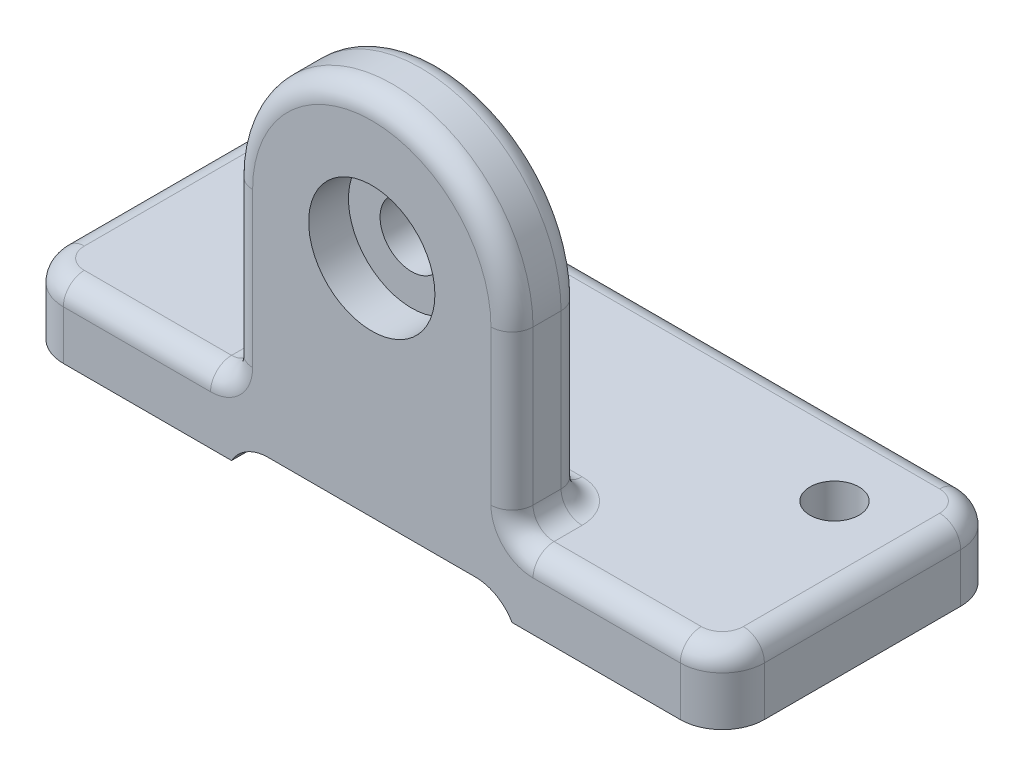
SolidWorks part; units mm, degrees
ref_plane "Front Plane" through (0, 0, 0) normal (0, 0, 1) x (1, 0, 0)
ref_plane "Top Plane" through (0, 0, 0) normal (0, 1, 0) x (1, 0, 0)
ref_plane "Right Plane" through (0, 0, 0) normal (1, 0, 0) x (0, 0, -1)
sketch "Sketch1" plane through (0, 0, 0) normal (0, 1, 0) x (1, 0, 0)
  line L1 (0, 0) -> (100, 0)
  line L2 (0, 0) -> (0, 40)
  line L3 (0, 40) -> (100, 40)
  line L4 (100, 0) -> (100, 40)
  dimension "D1" = 100
  dimension "D2" = 40
extrude "Base Plate" add sketch "Sketch1" along normal blind 10
sketch "Sketch2" plane through (0, 0, 0) normal (0, 0, 1) x (1, 0, 0)
  line L0 (30, 0) -> (30, 35)
  line L1 (0, 0) -> (100, 0) construction
  line L2 (70, 35) -> (70, 0)
  line L3 (70, 0) -> (30, 0)
  line L4 (0, 10) -> (0, 0) construction
  arc A0 (30, 35) -> (70, 35) centre (50, 35) cw
  dimension "D1" = 20
  dimension "D2" = 50
  dimension "D3" = 35
extrude "Vert Boss" add sketch "Sketch2" against normal blind 10
sketch "Sketch5" plane through (0, 0, 0) normal (0, 0, 1) x (1, 0, 0)
  line L0 (0, 0) -> (100, 0) construction
  line L1 (30, 0) -> (70, 0)
  line L2 (30, 0) -> (30, 3)
  line L3 (30, 3) -> (70, 3)
  line L4 (70, 0) -> (70, 3)
  line L5 (30, 35) -> (30, 10) construction
  line L6 (70, 10) -> (70, 35) construction
  dimension "D1" = 3
extrude "Slot" cut sketch "Sketch5" against normal through all
hole_wizard "Ø7.0 (7) Diameter Hole1" positions "Sketch9" profile "Sketch8" hole size "Ø7.0" standard "Ansi Metric" end condition through all
sketch "Sketch9" plane through (0, 10, 0) normal (0, 1, 0) x (-1, 0, 0)
  line L0 (-100, 0) -> (-100, -40) construction
  line L1 (-100, -40) -> (0, -40) construction
  line L2 (0, -40) -> (0, 0) construction
  point P0 (-88, -28)
  point P1 (-12, -28)
  dimension "D1" = 12
  dimension "D2" = 12
  dimension "D3" = 12
sketch "Sketch8" plane through (88, 10, -28) normal (1, 0, 0) x (0, 0, 1)
  line L0 (0, 0) -> (0, 10)
  line L1 (0, 10) -> (3.5, 10)
  line L2 (3.5, 10) -> (3.5, 0)
  line L5 (3.5, 0) -> (0, 0)
  line L11 (0, -6.35) -> (0, 107.95) construction
  dimension "Thru Hole Dia." = 7
  dimension "Thru Hole Depth" = 10
hole_wizard "CBORE for M8 Hex Head Bolt1" positions "Sketch4" profile "Sketch3" counterbore size "M8" standard "Ansi Metric" end condition through all
sketch "Sketch4" plane through (0, 0, 0) normal (0, 0, 1) x (1, 0, 0)
  point P0 (50, 35)
sketch "Sketch3" plane through (50, 35, 0) normal (1, 0, 0) x (0, -1, 0)
  line L0 (0, 0) -> (0, 40)
  line L1 (0, 40) -> (4.5, 40)
  line L3 (4.5, 40) -> (4.5, 5.68)
  line L4 (4.5, 5.68) -> (9.005, 5.68)
  line L5 (9.005, 5.68) -> (9.005, 0)
  line L7 (9.005, 0) -> (0, 0)
  line L11 (0, -6.35) -> (0, 107.95) construction
  dimension "Thru Hole Dia." = 9
  dimension "Thru Hole Depth" = 40
  dimension "C'Bore Dia." = 18.01
  dimension "C'Bore Depth" = 5.68
fillet "Fillet1" radius 6 6 edges at (70, 3, -20) (30, 3, -20) (0, 5, 0) (0, 5, -40) (100, 5, -40) (100, 5, 0)
fillet "Fillet2" radius 3 18 edges at (1.7574, 10, -38.2426) (0, 10, -20) (50, 10, -40) (1.7574, 10, -1.7574) (98.2426, 10, -38.2426) (18, 10, 0) (100, 10, -20) (30, 10, -5) (98.2426, 10, -1.7574) (50, 10, -10) (82, 10, 0) (70, 22.5, -10) (30, 22.5, -10) (70, 22.5, 0) (30, 22.5, 0) (70, 10, -5) (50, 55, -10) (50, 55, 0)
